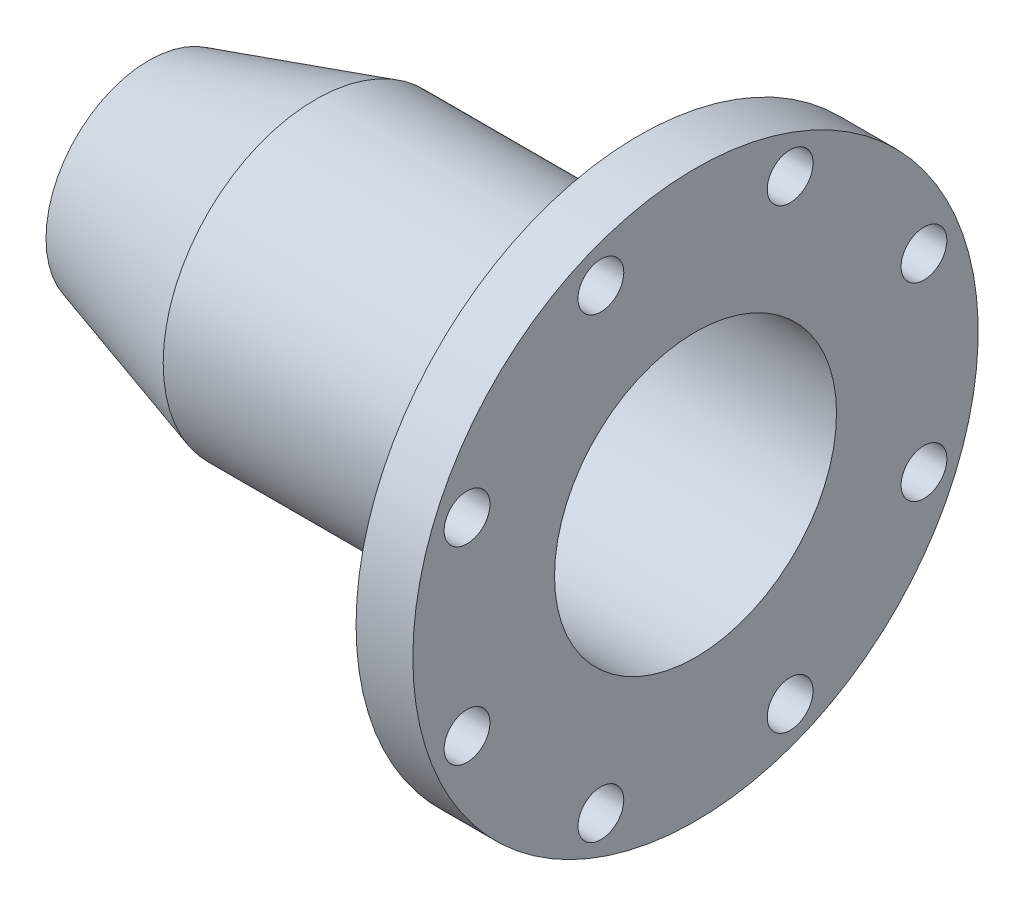
SolidWorks part; units mm, degrees
ref_plane "Front Plane" through (0, 0, 0) normal (0, 0, 1) x (1, 0, 0)
ref_plane "Top Plane" through (0, 0, 0) normal (0, 1, 0) x (1, 0, 0)
ref_plane "Right Plane" through (0, 0, 0) normal (1, 0, 0) x (0, 0, -1)
sketch "Sketch1" plane through (0, 0, 0) normal (0, 0, 1) x (1, 0, 0)
  line L0 (0, 0) -> (541.4119, 0) construction
  line L1 (266.7, 68.795) -> (266.7, 137.92)
  line L2 (266.7, 137.92) -> (239.01, 137.92)
  line L3 (239.01, 137.92) -> (239.01, 74.295)
  line L4 (239.01, 74.295) -> (81.28, 74.295)
  line L5 (239.01, 68.795) -> (82.0785, 68.795)
  line L6 (239.01, 68.795) -> (266.7, 68.795)
  line L7 (81.28, 74.295) -> (0, 50.1868)
  line L8 (82.0785, 68.795) -> (0, 44.45)
  line L9 (0, 50.1868) -> (0, 44.45)
  line L10 (239.01, 74.295) -> (266.7, 74.295)
  dimension "D2" = 27.69
  dimension "D3" = 74.295
  dimension "D4" = 185.42
  dimension "D5" = 266.7
  dimension "D6" = 5.5
  dimension "D7" = 5.5
  dimension "D1" = 44.45
revolve "Revolve1" add sketch "Sketch1" angle 360 about L0 region at (252.855, 71.4786, 0) region at (252.855, 106.1075, 0)
sketch "Sketch3" plane through (266.7, 0, 0) normal (1, 0, 0) x (0, 0, -1)
  line L0 (0, 0) -> (0, 120.65) construction
  line L1 (0, 0) -> (-46.1708, 111.4661) construction
  circle A0 centre (0, 0) radius 120.65 construction
  dimension "D1" = 241.3
  dimension "D2" = 22.5
hole_wizard "1/16 (0.88) Diameter Hole1" positions "3DSketch2" profile "Sketch7" hole size "1/16" standard "ANSI Inch" end condition through all
sketch3d "3DSketch2"
  point P0 (266.7, 111.4661, 46.1708)
sketch "Sketch7" plane through (266.7, 111.4661, 46.1708) normal (0, 1, 0) x (0, 0, -1)
  line L0 (0, 0) -> (0, 266.7)
  line L1 (0, 266.7) -> (11.176, 266.7)
  line L2 (11.176, 266.7) -> (11.176, 0)
  line L5 (11.176, 0) -> (0, 0)
  line L11 (0, -6.35) -> (0, 107.95) construction
  dimension "Thru Hole Dia." = 22.352
  dimension "Thru Hole Depth" = 266.7
pattern_circular "CirPattern1" count 8 over 360 about axis through (0, 0, 0) along (-1, 0, 0) of "1/16 (0.88) Diameter Hole1"
equation "\"Wall Thickness\"= 5.5"
equation "\"D6@Sketch1\"=\"Wall Thickness\""
equation "\"Nozzle diameter\"= 3.5 * 25.4"
equation "\"D7@Sketch1\"=\"Wall Thickness\""
equation "\"D1@Sketch1\"=\"Nozzle diameter\"/2"
